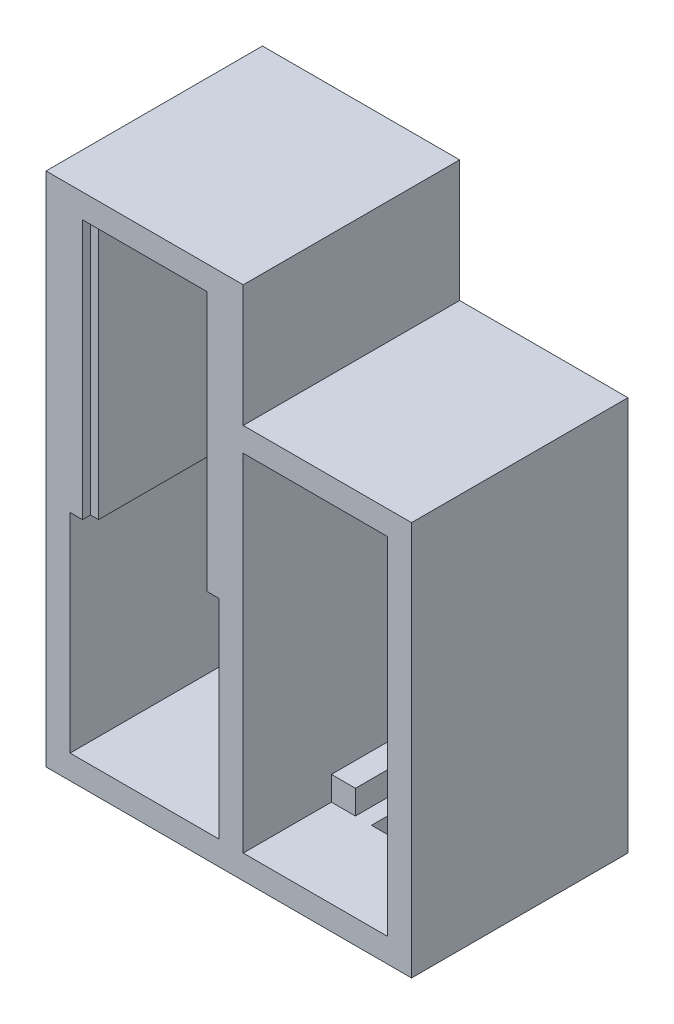
SolidWorks part; units mm, degrees
ref_plane "Front Plane" through (0, 0, 0) normal (0, 0, 1) x (1, 0, 0)
ref_plane "Top Plane" through (0, 0, 0) normal (0, 1, 0) x (1, 0, 0)
ref_plane "Right Plane" through (0, 0, 0) normal (1, 0, 0) x (0, 0, -1)
sketch "Sketch1" plane through (0, 0, 0) normal (0, 0, 1) x (1, 0, 0)
  line L0 (0, 0) -> (-18.6, 0)
  line L1 (-18.6, 0) -> (-18.6, 26)
  line L2 (-18.6, 26) -> (0, 26)
  line L3 (0, 26) -> (0, 0)
  line L4 (-18.6, 26) -> (-17.05, 26)
  line L5 (-17.05, 26) -> (-17.05, 58.4)
  line L6 (-17.05, 58.4) -> (-1.55, 58.4)
  line L7 (-1.55, 58.4) -> (-1.55, 26)
  line L8 (-18.6, 0) -> (-21.6, 0)
  line L9 (-21.6, 0) -> (-21.6, 58.4)
  line L10 (-21.6, 58.4) -> (-21.6, 61.4)
  line L11 (-21.6, 61.4) -> (-18.6, 61.4)
  line L12 (-18.6, 61.4) -> (-18.6, 26)
  line L13 (-18.6, 61.4) -> (0, 61.4)
  line L14 (0, 61.4) -> (0, 26)
  line L15 (0, 61.4) -> (3, 61.4)
  line L16 (3, 61.4) -> (3, 0)
  line L17 (3, 0) -> (0, 0)
  line L18 (3, 0) -> (3, -3)
  line L19 (3, -3) -> (-21.6, -3)
  line L20 (-21.6, -3) -> (-21.6, 0)
  line L21 (-21.6, 58.4) -> (3, 58.4)
  line L22 (-17.05, 58.4) -> (-16.05, 58.4)
  line L23 (-16.05, 58.4) -> (-16.05, 26)
  line L24 (-16.05, 26) -> (-17.05, 26)
  line L25 (-1.55, 58.4) -> (-2.55, 58.4)
  line L26 (-2.55, 58.4) -> (-2.55, 26)
  line L27 (-2.55, 26) -> (-1.55, 26)
extrude "Boss-Extrude1" add sketch "Sketch1" along normal blind 3 contours L23 L6 L5 L2 | L26 L21 L23 L2 | L6 L26 L2 L7 | L21 L7 L2 L14 | L21 L12 L2 L5 | L21 L9 L8 L1 L12 | L10 L21 L12 L11 | L12 L21 L6 L14 L13 | L14 L21 L16 L15 | L21 L14 L3 L17 L16 | L3 L2 L1 L0 | L20 L19 L18 L17 L0 L8 region at (-9.3, -1.5, 0) region at (-9.3, 13, 0) region at (1.5, 29.2, 0) region at (-20.1, 29.2, 0) region at (-0.775, 42.2, 0) region at (-17.825, 42.2, 0) region at (-2.05, 42.2, 0) region at (-9.3, 59.9, 0) region at (1.5, 59.9, 0) region at (-16.55, 42.2, 0) region at (-20.1, 59.9, 0) region at (-9.3, 42.2, 0)
extrude "Boss-Extrude2" add sketch "Sketch1<5>" along normal blind 26 contours L10 L21 L12 L11 | L12 L21 L6 L14 L13 | L6 L26 L2 L7 | L21 L7 L2 L14 | L23 L6 L5 L2 | L21 L12 L2 L5 | L21 L9 L8 L1 L12 | L14 L21 L16 L15 | L21 L14 L3 L17 L16 | L20 L19 L18 L17 L0 L8 region at (-9.3, -1.5, 0) region at (1.5, 29.2, 0) region at (-20.1, 29.2, 0) region at (-0.775, 42.2, 0) region at (-17.825, 42.2, 0) region at (-2.05, 42.2, 0) region at (-9.3, 59.9, 0) region at (1.5, 59.9, 0) region at (-16.55, 42.2, 0) region at (-20.1, 59.9, 0)
sketch "Sketch1<5>" plane through (0, 0, 0) normal (0, 0, 1) x (1, 0, 0) same geometry as "Sketch1"
extrude "Boss-Extrude4" add sketch "Sketch1<7>" along normal blind 35 contours L20 L19 L18 L17 L0 L8 region at (-9.3, -1.5, 0)
sketch "Sketch1<7>" plane through (0, 0, 0) normal (0, 0, 1) x (1, 0, 0) same geometry as "Sketch1"
extrude "Boss-Extrude5" add sketch "Sketch1<8>" along normal blind 27 contours L21 L12 L2 L5 | L21 L9 L8 L1 L12 | L10 L21 L12 L11 | L12 L21 L6 L14 L13 | L14 L21 L16 L15 | L21 L14 L3 L17 L16 | L21 L7 L2 L14 | L20 L19 L18 L17 L0 L8 region at (-9.3, -1.5, 0) region at (1.5, 29.2, 0) region at (-20.1, 29.2, 0) region at (-0.775, 42.2, 0) region at (-17.825, 42.2, 0) region at (-9.3, 59.9, 0) region at (1.5, 59.9, 0) region at (-20.1, 59.9, 0)
sketch "Sketch1<8>" plane through (0, 0, 0) normal (0, 0, 1) x (1, 0, 0) same geometry as "Sketch1"
sketch "Sketch2" plane through (0, 0, 0) normal (0, 0, -1) x (-1, 0, 0)
  line L0 (0, 0) -> (-3, 0)
  line L1 (-3, 0) -> (-3, -3)
  line L2 (-3, -3) -> (-21, -3)
  line L3 (-21, -3) -> (-21, 0)
  line L4 (-21, 0) -> (-3, 0)
  line L5 (-21, -3) -> (-24, -3)
  line L6 (-24, -3) -> (-24, 0)
  line L7 (-24, 0) -> (-21, 0)
  line L8 (-21, 0) -> (-21, 43.2)
  line L9 (-21, 43.2) -> (-3, 43.2)
  line L10 (-3, 61.4) -> (-3, 0) construction
  line L11 (-24, 0) -> (-24, 43.2)
  line L12 (-24, 43.2) -> (-24, 46.2)
  line L13 (-24, 46.2) -> (-3, 46.2)
  line L14 (-3, 46.2) -> (-3, 0)
  line L15 (-21, 43.2) -> (-21, 40.2)
  line L16 (-21, 40.2) -> (-16, 40.2)
  line L17 (-16, 40.2) -> (-16, 43.2)
  line L18 (-3, 43.2) -> (-3, 40.2)
  line L19 (-3, 40.2) -> (-8, 40.2)
  line L20 (-8, 40.2) -> (-8, 43.2)
  line L21 (-21, 0) -> (-18, 0)
  line L22 (-18, 0) -> (-18, 3)
  line L23 (-18, 3) -> (-21, 3)
  line L24 (-3, 0) -> (-3, 3)
  line L25 (-3, 3) -> (-6, 3)
  line L26 (-6, 3) -> (-6, 0)
  line L27 (-21, -3) -> (-16, -3)
  line L28 (-16, -3) -> (-16, 0)
  line L29 (-3, -3) -> (-8, -3)
  line L30 (-8, -3) -> (-8, 0)
  line M8 (-3, 61.4) -> (-3, -3)
extrude "Boss-Extrude6" add sketch "Sketch2" against normal blind 3 contours L26 L25 L14 L19 L20 L9 L17 L16 L8 L23 L22 L4 region at (12, 21.2694, 0)
extrude "Boss-Extrude7" add sketch "Sketch2<3>" against normal blind 2 contours L25 L26 L4 M8 | L30 L2 L4 M8 | L22 L23 L8 L4 | L2 L28 L4 L3 | L7 L6 L5 L3 | L13 L12 L11 L7 L8 L9 M8 | L16 L17 L9 L8 | L20 L19 L9 M8 region at (5.5, -1.5, 0) region at (4.5, 1.5, 0) region at (5.5, 41.7, 0) region at (18.5, -1.5, 0) region at (5.5, 43.7075, 0) region at (22.5, -1.5, 0) region at (19.5, 1.5, 0) region at (18.5, 41.7, 0)
sketch "Sketch2<3>" plane through (0, 0, 0) normal (0, 0, -1) x (-1, 0, 0) same geometry as "Sketch2"
extrude "Boss-Extrude8" add sketch "Sketch2<4>" against normal blind 11 contours L2 L30 L4 L28 region at (12, -1.5, 0)
sketch "Sketch2<4>" plane through (0, 0, 0) normal (0, 0, -1) x (-1, 0, 0) same geometry as "Sketch2"
extrude "Boss-Extrude9" add sketch "Sketch2<5>" against normal blind 27 contours L30 L2 L4 M8 | L2 L28 L4 L3 | L7 L6 L5 L3 | L13 L12 L11 L7 L8 L9 M8 region at (5.5, -1.5, 0) region at (18.5, -1.5, 0) region at (5.5, 43.7075, 0) region at (22.5, -1.5, 0)
sketch "Sketch2<5>" plane through (0, 0, 0) normal (0, 0, -1) x (-1, 0, 0) same geometry as "Sketch2"
sketch "Sketch5" plane through (0, 0, 0) normal (0, 0, -1) x (-1, 0, 0)
  line L0 (21.6, -3) -> (52.2188, -3)
  line L1 (52.2188, -3) -> (52.2188, 57.4)
  line L2 (52.2188, 57.4) -> (21.6, 57.4)
  line L3 (21.6, 0) -> (21.6, 61.4) construction
  line L4 (21.6, 57.4) -> (21.6, 54.4)
  line L5 (21.6, 54.4) -> (21.6, 0)
  line L6 (21.6, 0) -> (21.6, -3)
  line L7 (21.6, 0) -> (52.2188, 0)
  line L8 (52.2188, -3) -> (55.2, -3)
  line L9 (55.2, -3) -> (55.2, 57.4)
  line L10 (55.2, 57.4) -> (52.2188, 57.4)
  line L11 (52.2188, 57.4) -> (52.2188, 54.4)
  line L12 (52.2188, 54.4) -> (21.6, 54.4)
  line M11 (21.6, -3) -> (21.6, 61.4)
extrude "Boss-Extrude11" add sketch "Sketch5" against normal blind 3 contours L12 L1 L2 M11 | L9 L10 L1 L8 | L7 L0 L1 M11 | L1 L12 L7 M11 region at (-36.9094, -1.5, 0) region at (-53.7094, 27.2, 0) region at (-36.9094, 27.2, 0) region at (-36.9094, 55.9, 0)
extrude "Cut-Extrude3" cut sketch "Sketch5<5>" against normal blind 3 contours L1 L12 L7 M11 region at (-36.9094, 27.2, 0)
sketch "Sketch5<5>" plane through (0, 0, 0) normal (0, 0, -1) x (-1, 0, 0) same geometry as "Sketch5"
extrude "Boss-Extrude12" add sketch "Sketch5<6>" against normal blind 27 contours L12 L1 L2 M11 | L9 L10 L1 L8 | L7 L0 L1 M11 region at (-36.9094, -1.5, 0) region at (-53.7094, 27.2, 0) region at (-36.9094, 55.9, 0)
sketch "Sketch5<6>" plane through (0, 0, 0) normal (0, 0, -1) x (-1, 0, 0) same geometry as "Sketch5"
sketch "Sketch6" plane through (0, 0, 27) normal (0, 0, 1) x (1, 0, 0)
  line L0 (-21.6, 54.4) -> (-21.6, 47.4)
  line L1 (-21.6, 0) -> (-21.6, 54.4) construction
  line L2 (-21.6, 47.4) -> (-52.2188, 47.4)
  line L3 (-52.2188, 0) -> (-52.2188, 54.4) construction
  line L4 (-52.2188, 47.4) -> (-52.2188, 0)
  line L5 (-52.2188, 0) -> (-21.6, 0)
  line L6 (-21.6, 0) -> (-21.6, 47.4)
  line M21 (-21.6, 0) -> (-52.2188, 0)
  line M22 (-52.2188, 0) -> (-52.2188, 54.4)
  line M24 (-21.6, 54.4) -> (-21.6, 0)
extrude "Boss-Extrude13" add sketch "Sketch6" against normal blind 3 contours L2 M24 M22 M21 region at (-36.9094, 23.7, 27)
sketch "Sketch7" plane through (0, -3, 0) normal (0, -1, 0) x (1, 0, 0)
  line L0 (-21.6, 27) -> (-21.6, 35)
  line L1 (-21.6, 35) -> (3, 35)
  line L2 (3, 35) -> (3, 27)
  line L3 (3, 27) -> (-21.6, 27)
extrude "Cut-Extrude4" cut sketch "Sketch7" against normal blind 3
sketch "Sketch8" plane through (8, 0, 0) normal (1, 0, 0) x (0, 0, -1)
  line L0 (-11, -3) -> (-16, -3)
  line L1 (-27, -3) -> (0, -3) construction
  line L2 (-16, -3) -> (-16, 0)
  line L3 (-27, 0) -> (-11, 0) construction
  line L4 (-16, 0) -> (-27, 0)
  line L5 (-27, 0) -> (-27, -3)
  line L6 (-27, -3) -> (-16, -3)
  line M1 (-27, -3) -> (-11, -3)
  line M3 (-11, 0) -> (-27, 0)
  line M4 (-27, 0) -> (-27, -3)
extrude "Boss-Extrude14" add sketch "Sketch8" along normal blind 8 contours L2 M1 M3 M4 region at (8, -1.5, 21.5)
extrude "Boss-Extrude15" add sketch "Sketch2<6>" against normal blind 16 contours L20 L19 L9 M8 | L16 L17 L9 L8 | L22 L23 L8 L4 | L25 L26 L4 M8 region at (4.5, 1.5, 0) region at (5.5, 41.7, 0) region at (19.5, 1.5, 0) region at (18.5, 41.7, 0)
sketch "Sketch2<6>" plane through (0, 0, 0) normal (0, 0, -1) x (-1, 0, 0) same geometry as "Sketch2"
sketch "Sketch9" plane through (0, 0, 27) normal (0, 0, 1) x (1, 0, 0)
  line L0 (-18.6, 0) -> (-18.6, -3)
  line L1 (-55.2, -3) -> (24, -3) construction
  line L2 (-18.6, -3) -> (-55.2, -3)
  line L3 (-55.2, -3) -> (-55.2, 0)
  line L4 (-55.2, -3) -> (-55.2, 57.4) construction
  line L5 (-55.2, 0) -> (-18.6, 0)
extrude "Boss-Extrude16" add sketch "Sketch9" along normal blind 15
sketch "Sketch10" plane through (0, -3, 0) normal (0, -1, 0) x (-1, 0, 0)
  line L0 (18.6, -27) -> (55.2, -27)
  line L1 (55.2, -42) -> (55.2, 0) construction
  line L2 (18.6, -27) -> (30.2563, -27)
  line L3 (30.2563, -27) -> (30.2563, -28.7)
  line L4 (30.2563, -28.7) -> (30.2563, -40.3018)
  line L5 (30.2563, -40.3018) -> (49.0563, -40.3018)
  line L6 (49.0563, -40.3018) -> (49.0563, -28.7)
  line L7 (49.0563, -28.7) -> (30.2563, -28.7)
  dimension "D1" = 1.7
extrude "Cut-Extrude5" cut sketch "Sketch10" against normal blind 15 contours L6 L7 L4 L5 region at (-39.6563, -3, 34.5009)
sketch "Sketch11" plane through (0, -3, 0) normal (0, -1, 0) x (-1, 0, 0)
  line L0 (18.6, -42) -> (18.6, -27)
  line L1 (18.6, -42) -> (3.6, -27)
  line L2 (18.6, -27) -> (-24, -27) construction
  line L3 (3.6, -27) -> (18.6, -27)
extrude "Boss-Extrude17" add sketch "Sketch11" against normal blind 3
sketch "Sketch12" plane through (-55.2, 0, 0) normal (-1, 0, 0) x (0, 0, 1)
  line L0 (27, 0) -> (42, 0)
  line L1 (42, 0) -> (27, 15)
  line L2 (27, 0) -> (27, 57.4) construction
  line L3 (27, 15) -> (27, 0)
extrude "Boss-Extrude18" add sketch "Sketch12" against normal blind 3
sketch "Sketch13" plane through (0, 0, 42) normal (0, 0, 1) x (1, 0, 0)
  line L0 (-21.6, 57.4) -> (-21.6, -3)
  line L1 (-55.2, -3) -> (-18.6, -3) construction
  line L2 (-21.6, -3) -> (-55.2, -3)
  line L3 (-55.2, -3) -> (-55.2, 57.4)
  line L4 (-55.2, 57.4) -> (-21.6, 57.4)
extrude "Cut-Extrude6" cut sketch "Sketch13" against normal blind 70
sketch "Sketch14" plane through (0, -3, 0) normal (0, -1, 0) x (-1, 0, 0)
  line L0 (3.6, -27) -> (21.6, -27)
  line L1 (21.6, -27) -> (21.6, -42)
  line L2 (21.6, -42) -> (18.6, -42)
  line L3 (18.6, -42) -> (3.6, -27)
extrude "Cut-Extrude7" cut sketch "Sketch14" against normal blind 70
